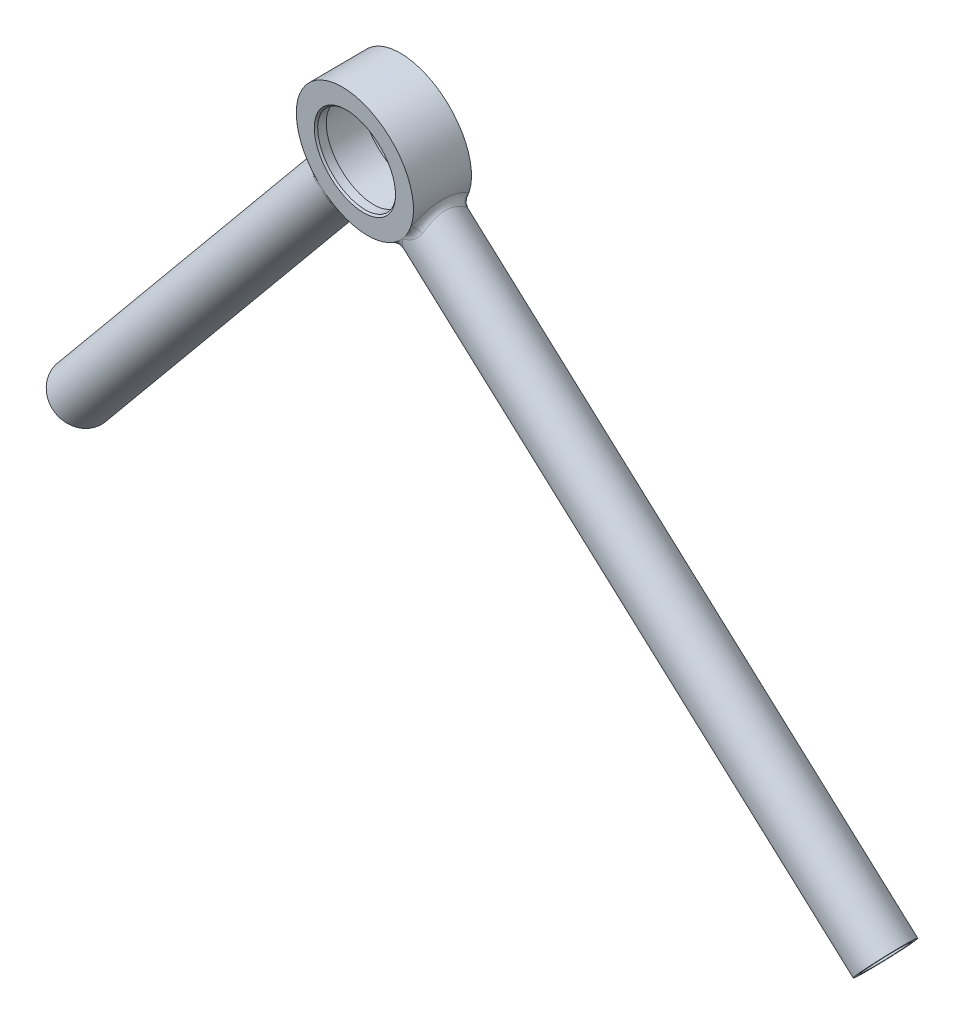
SolidWorks part; units mm, degrees
ref_plane "Ground Plane" through (0, 0, 0) normal (0, 0, 1) x (1, 0, 0)
ref_plane "Side Plane" through (0, 0, 0) normal (0, 1, 0) x (1, 0, 0)
ref_plane "Rear Axle Centerline" through (0, 0, 0) normal (1, 0, 0) x (0, 0, -1)
sketch "Chassis Side View" plane through (0, 0, 0) normal (0, 1, 0) x (1, 0, 0)
  line L0 (0, -381) -> (2300, -381) construction
  line L1 (1150, -381) -> (1150, -856.742)
  line L2 (2150, -381) -> (2150, -1062.9307) construction
  line L3 (-753.0356, 0) -> (753.0356, 0) construction
  line L4 (2450, -381) -> (2450, -1062.9307) construction
  dimension "D1" = 2300
  dimension "D2" = 475.742
  dimension "D3" = 1150
  dimension "D4" = 381
  dimension "D5" = 150
  dimension "D6" = 150
ref_plane "Front Axle Centerline" through (2300, 0, 0) normal (1, 0, 0) x (0, 0, -1)
sketch "Front Wheel Assy Constraints" plane through (2300, 0, 0) normal (1, 0, 0) x (0, 0, -1)
  line L0 (0, 727.5) -> (0, 822.5)
  line L1 (0, 822.5) -> (-271.78, 822.5)
  line L2 (-271.78, 822.5) -> (-551.18, 822.5)
  line L3 (-551.18, 822.5) -> (-551.18, 727.5)
  line L4 (-551.18, 775) -> (0, 775) construction
  line L5 (-271.78, 822.5) -> (-271.78, 775) construction
  line L6 (-551.18, 727.5) -> (-445.4516, 727.5)
  line L7 (-445.4516, 727.5) -> (-445.4516, 798.5)
  line L8 (-445.4516, 798.5) -> (-105.7284, 798.5)
  line L9 (-105.7284, 798.5) -> (-105.7284, 727.5)
  line L10 (-105.7284, 727.5) -> (0, 727.5)
  line L11 (0, 0) -> (-673.9047, 0) construction
  line L13 (0, 753.0356) -> (0, -753.0356) construction
  dimension "D1" = 95
  dimension "D2" = 279.4
  dimension "D3" = 271.78
  dimension "D4" = 23.5
  dimension "D5" = 1550
sketch "Front Sus Front View" plane through (2300, 0, 0) normal (1, 0, 0) x (0, 0, -1)
  line L0 (0, 775) -> (0, 768.65) construction
  line L1 (0, 753.0356) -> (0, -753.0356) construction
  line L2 (0, 768.65) -> (-762, 634.2888) construction
  line L3 (0, 768.65) -> (-745.3671, 768.65) construction
  line L4 (-366.7919, -1090.2477) -> (-525.9451, 520.8571) construction
  line L5 (-366.7919, -1090.2477) -> (-379.5678, 520.8571) construction
  line L6 (-366.7919, -1090.2477) -> (0, 775) construction
  line L7 (-525.9451, 520.8571) -> (-541, 673.2571)
  line L8 (-379.5678, 520.8571) -> (-381, 701.4694)
  line L9 (0, 0) -> (-152.4, 0) construction
  line L13 (-525.9451, 520.8571) -> (-379.5678, 520.8571) construction
  dimension "D1" = 6.35
  dimension "D2" = 10
  dimension "D3" = 152.4
  dimension "D4" = 1865.2477
  dimension "D7" = 541
  dimension "D8" = 153.1418
ref_plane "Fron Wheel Side View Plane" through (0, 775, 0) normal (0, 1, 0) x (1, 0, 0)
sketch "Front SVSA" plane through (0, 775, 0) normal (0, 1, 0) x (1, 0, 0)
  line L0 (2271.684, -676.7175) -> (2328.316, 133.1575)
  line L1 (2300, 0) -> (2300, -771.0839) construction
  line L2 (2300, 0) -> (-2450.054, -116.0888) construction
  line L3 (-2450.054, -116.0888) -> (2298.2335, -297.0415) construction
  line L4 (-753.0356, 0) -> (753.0356, 0) construction
  point P5 (2300, -271.78)
  dimension "D1" = 4
  dimension "D2" = 1.4
  dimension "D3" = 4750.054
sketch3d "Front Chassis Side Axes"
  line L0 (2300, 520.8571, 379.5678) -> (2300, 701.4694, 381) construction
  line L1 (2300, 520.8571, 525.9451) -> (2300, 673.2571, 541) construction
  line L2 (2300, 520.8571, 379.5678) -> (2300, 701.4694, 381) construction
  line L3 (2300, 520.8571, 525.9451) -> (2300, 673.2571, 541) construction
  line L4 (2300, 673.2571, 541) -> (2300, 775, 551.0507) construction
  line L5 (2300, 701.4694, 381) -> (2300, 775, 381.5831) construction
  line L6 (2300, 775, 0) -> (2300, 775, 771.0839) construction
  line L7 (-2450.054, 775, 116.0888) -> (2349.7917, 775, 555.6101) construction
  line L8 (-2450.054, 775, 116.0888) -> (2349.9221, 775, 384.3734) construction
  line L9 (2349.9221, 775, 384.3734) -> (2177.377, 520.8571, 372.714) construction
  line L10 (2349.7917, 775, 555.6101) -> (2225.4174, 520.8571, 519.1156) construction
  line L11 (2300, 520.8571, 525.9451) -> (2300, 520.8571, 519.1156) construction
  line L12 (2300, 520.8571, 519.1156) -> (2225.4174, 520.8571, 519.1156) construction
  line L13 (2598.7501, 520.8571, 553.3017) -> (1702.4998, 520.8571, 471.2321)
  line L14 (2300, 520.8571, 379.5678) -> (2300, 520.8571, 372.714) construction
  line L15 (2300, 520.8571, 372.714) -> (2177.377, 520.8571, 372.714) construction
  line L16 (2599.5325, 520.8571, 396.3095) -> (1700.935, 520.8571, 346.0843)
  dimension "D1" = 50
  dimension "D2" = 50
  dimension "D3" = 600
  dimension "D4" = 300
  dimension "D5" = 600
  dimension "D6" = 300
sketch3d "Front Left Control Arm"
  line L0 (2300, 520.8571, 379.5678) -> (2300, 701.4694, 381) construction
  line L2 (2300, 520.8571, 379.5678) -> (2300, 701.4694, 381) construction
  line L3 (2300, 520.8571, 525.9451) -> (2300, 673.2571, 541) construction
  line L4 (2598.7501, 520.8571, 553.3017) -> (1702.4998, 520.8571, 471.2321) construction
  line L5 (2599.5325, 520.8571, 396.3095) -> (1700.935, 520.8571, 346.0843) construction
  line L6 (2598.7501, 520.8571, 553.3017) -> (1702.4998, 520.8571, 471.2321) construction
  line L7 (2599.5325, 520.8571, 396.3095) -> (1700.935, 520.8571, 346.0843) construction
  line L8 (2450, 520.8571, 539.6806) -> (2280.5957, 673.2571, 539.2232)
  line L9 (2280.5957, 673.2571, 539.2232) -> (2150, 520.8571, 512.2097)
  line L10 (2300, 520.8571, 525.9451) -> (2300, 673.2571, 541) construction
  line L11 (2300, 673.2571, 541) -> (2280.5957, 673.2571, 539.2232) construction
  line L12 (2271.684, 775, 676.7175) -> (2328.316, 775, -133.1575) construction
  line L13 (2150, 0, 512.2097) -> (2150, 520.8571, 512.2097) construction
  line L14 (2292.3517, 701.4694, 380.5725) -> (2292.3517, 775, 381.1556) construction
  line L15 (2150, 0, 381) -> (2150, 0, 1062.9307) construction
  line L16 (2450, 0, 539.6806) -> (2450, 520.8571, 539.6806) construction
  line L17 (2450, 0, 381) -> (2450, 0, 1062.9307) construction
  line L18 (2450, 520.8571, 387.9517) -> (2292.3517, 701.4694, 380.5725)
  line L19 (2292.3517, 701.4694, 380.5725) -> (2150, 520.8571, 371.1838)
  line L20 (2300, 701.4694, 381) -> (2292.3517, 701.4694, 380.5725) construction
  line L21 (2450, 0, 387.9517) -> (2450, 520.8571, 387.9517) construction
  line L22 (2150, 0, 371.1838) -> (2150, 520.8571, 371.1838) construction
  line L23 (2280.5957, 673.2571, 539.2232) -> (2280.5957, 775, 549.2738) construction
sketch3d "Front Control Arm"
  line L0 (2450, 520.8571, 387.9517) -> (2292.3517, 701.4694, 380.5725) construction
  line L1 (2292.3517, 701.4694, 380.5725) -> (2150, 520.8571, 371.1838) construction
  line L2 (2280.5957, 673.2571, 539.2232) -> (2150, 520.8571, 512.2097) construction
  line L3 (2450, 520.8571, 539.6806) -> (2280.5957, 673.2571, 539.2232) construction
  line L4 (2450, 520.8571, 387.9517) -> (2292.3517, 701.4694, 380.5725)
  line L5 (2292.3517, 701.4694, 380.5725) -> (2150, 520.8571, 371.1838)
  line L6 (2280.5957, 673.2571, 539.2232) -> (2150, 520.8571, 512.2097)
  line L7 (2450, 520.8571, 539.6806) -> (2280.5957, 673.2571, 539.2232)
  line L8 (2450, -520.8571, 539.6806) -> (2280.5957, -673.2571, 539.2232)
  line L9 (2280.5957, -673.2571, 539.2232) -> (2150, -520.8571, 512.2097)
  line L10 (2292.3517, -701.4694, 380.5725) -> (2150, -520.8571, 371.1838)
  line L11 (2450, -520.8571, 387.9517) -> (2292.3517, -701.4694, 380.5725)
ref_plane "Max Droop Plane" through (0, 0, -25.4) normal (0, 0, 1) x (1, 0, 0)
sketch3d "Shock"
  line L0 (2292.3517, 701.4694, 380.5725) -> (2293.5626, 664.4705, 414.2387) construction
  line L1 (2300, 520.8571, 525.9451) -> (2298.2629, 520.8571, 544.9158) construction
  line L2 (2150, 520.8571, 512.2097) -> (2450, 520.8571, 539.6806) construction
  line L3 (2300, 520.8571, 525.9451) -> (2300, 230.5152, 525.9451) construction
  line L4 (2293.5626, 664.4705, 414.2387) -> (2298.2629, 520.8571, 544.9158)
  dimension "D1" = 50.038
  dimension "D2" = 19.05
sketch3d "Parametric Analysis"
  line L2 (2300, 822.5, 0) -> (2300, 822.5, 271.78) construction
  line L3 (2300.4137, 822.5, 271.7939) -> (2300.4137, 822.5, -88.8537) construction
  line L4 (2450, 520.8571, 387.9517) -> (2292.3526, 701.4695, 380.5568)
  line L5 (2292.3526, 701.4695, 380.5568) -> (2150, 520.8571, 371.1838)
  line L6 (2450, 520.8571, 539.6806) -> (2280.5972, 673.2586, 539.2077)
  line L7 (2280.5972, 673.2586, 539.2077) -> (2150, 520.8571, 512.2097)
  line L8 (2292.3517, 701.4694, 380.5725) -> (2300, 822.5, 271.78) construction
  line L9 (2450, 520.8571, 387.9517) -> (2292.3517, 701.4694, 380.5725) construction
  line L10 (2292.3517, 701.4694, 380.5725) -> (2150, 520.8571, 371.1838) construction
  line L11 (2450, 520.8571, 539.6806) -> (2280.5957, 673.2571, 539.2232) construction
  line L12 (2280.5957, 673.2571, 539.2232) -> (2150, 520.8571, 512.2097) construction
  line L13 (2280.5957, 673.2571, 539.2232) -> (2292.3517, 701.4694, 380.5725) construction
  line L14 (2300, 822.5, 271.78) -> (2280.5957, 673.2571, 539.2232) construction
  line L15 (2300, 822.5, 271.78) -> (2300.4132, 720.8156, 271.78) construction
  line L16 (2280.5972, 673.2586, 539.2077) -> (2300.4137, 822.5, 271.7939) construction
  line L17 (2300.4137, 822.5, 271.7939) -> (2292.3526, 701.4695, 380.5568) construction
  line L18 (2280.5972, 673.2586, 539.2077) -> (2292.3526, 701.4695, 380.5568) construction
  line L19 (2300.4137, 822.5, 271.7939) -> (2300.4137, 720.8148, 271.7641) construction
  line L23 (2292.3517, 701.4694, 380.5725) -> (2265.8007, 667.7821, 378.8214) construction
  line L30 (2265.8007, 667.7821, 378.8214) -> (2325.2406, 663.7898, 382.112) construction
  line L31 (2325.2406, 663.7898, 382.112) -> (2293.5626, 664.4705, 414.2387) construction
  line L32 (2292.3517, 701.4694, 380.5725) -> (2325.2406, 663.7898, 382.112) construction
  line L33 (2293.5626, 664.4705, 414.2387) -> (2265.8007, 667.7821, 378.8214) construction
  line L34 (2292.3526, 701.4695, 380.5568) -> (2293.5633, 664.4722, 414.2247) construction
  line L35 (2292.3517, 701.4694, 380.5725) -> (2293.5626, 664.4705, 414.2387) construction
  line L39 (2300.4137, 822.5, 271.7939) -> (2300.4137, 822.5798, 0.014)
  line L40 (2300.4137, 822.5798, 0.014) -> (2300.4137, 727.5798, -0.014)
  line L41 (2300, 727.5, 0) -> (2300, 822.5, 0) construction
  line L42 (2298.2629, 520.8571, 544.9158) -> (2293.5633, 664.4722, 414.2247)
  point P5 (2300.4137, 775.0798, 0)
  dimension "D1" = 25.4
  dimension "D2" = 194.2357
  dimension "D3" = 0.0798
  dimension "D4" = 0.017
sketch3d "3DSketch1"
  line L1 (2280.5972, 673.2586, 539.2077) -> (2150, 520.8571, 512.2097) construction
  line L2 (2450, 520.8571, 539.6806) -> (2280.5972, 673.2586, 539.2077) construction
  line L6 (2280.5972, 673.2586, 539.2077) -> (2150, 520.8571, 512.2097)
  line L7 (2450, 520.8571, 539.6806) -> (2280.5972, 673.2586, 539.2077)
  line L10 (2450, 520.8571, 539.6806) -> (2450, 470.0571, 539.6806) construction
  line L11 (2150, 520.8571, 512.2097) -> (2150, 470.0571, 512.2097) construction
  line L12 (2298.2629, 520.8571, 544.9158) -> (2298.2629, 470.0571, 544.9158) construction
  line L27 (2300, 775, 551.18) -> (2300, 775, 0) construction
  dimension "D1" = 50.8
  dimension "D2" = 304.9478
  dimension "D3" = 544.9185
ref_plane "Plane1" through (0, 718.612, 0) normal (0, 1, 0) x (1, 0, 0)
ref_plane "Plane3" through (-23.7383, -25.582, 259.237) normal (-0.0908, -0.0978, 0.9911) x (0.9959, -0.0089, 0.0903)
sketch "Sketch3" plane through (-23.7383, -25.582, 259.237) normal (-0.0908, -0.0978, 0.9911) x (0.9959, -0.0089, 0.0903)
  circle A0 centre (2313.8835, 722.9571) radius 19.05
  dimension "D1" = 38.1
extrude "Boss-Extrude1" add sketch "Sketch3" along normal mid plane 15.875
sketch "Sketch4" plane through (-24.4586, -26.3583, 267.1036) normal (-0.0908, -0.0978, 0.9911) x (0.9959, -0.0089, 0.0903)
  circle A0 centre (2313.8835, 722.9571) radius 12.7
  dimension "D1" = 25.4
extrude "Cut-Extrude1" cut sketch "Sketch4" against normal blind 15.875
sketch "Sketch5" plane through (-23.7383, -25.582, 259.237) normal (-0.0908, -0.0978, 0.9911) x (0.9959, -0.0089, 0.0903)
  line L0 (2313.8835, 722.9571) -> (2182.7452, 568.6409) construction
  line L1 (2483.9882, 571.3387) -> (2313.8835, 722.9571) construction
  point P0 (2280.9874, 684.2468)
  point P1 (2351.806, 689.1559)
  dimension "D1" = 50.8
  dimension "D2" = 50.8
sketch "Sketch12" plane through (-23.7383, -25.582, 259.237) normal (-0.0908, -0.0978, 0.9911) x (0.9959, -0.0089, 0.0903)
  line L0 (2313.8835, 722.9571) -> (2182.7452, 568.6409) construction
  line L1 (2483.9882, 571.3387) -> (2313.8835, 722.9571) construction
  point P0 (2200.5604, 589.6049)
  point P1 (2463.4509, 589.6441)
  dimension "D1" = 174.9998
  dimension "D2" = 200.3566
ref_plane "Plane4" through (2167.7417, 541.561, 515.8774) normal (-0.6449, -0.7526, -0.1333) x (-0.7643, 0.635, 0.1125)
ref_plane "Plane5" through (2429.5474, 539.2571, 539.6235) normal (-0.7434, 0.6688, -0.0021) x (-0.0015, 0.0014, 1)
sketch "Sketch6" plane through (2167.7417, 541.561, 515.8774) normal (-0.6449, -0.7526, -0.1333) x (-0.7643, 0.635, 0.1125)
  circle A0 centre (0, 0) radius 7.9375
  circle A1 centre (0, 0) radius 6.35
  dimension "D1" = 15.875
extrude "Boss-Extrude2" add sketch "Sketch6" against normal up to body
sketch "Sketch7" plane through (2429.5474, 539.2571, 539.6235) normal (-0.7434, 0.6688, -0.0021) x (-0.0015, 0.0014, 1)
  circle A0 centre (0, 0) radius 7.9375
  circle A1 centre (0, 0) radius 6.35
  dimension "D1" = 15.875
extrude "Boss-Extrude3" add sketch "Sketch7" along normal up to body
fillet "Fillet1" radius 2.54 4 edges at (2288.2371, 655.8515, 537.9491) (2263.3363, 665.0976, 538.3666) (2263.3363, 665.0976, 538.3666) (2288.2371, 655.8515, 537.9491)
ref_plane "Plane6" through (1321.5606, 1542.207, 273.2032) normal (-0.6449, -0.7526, -0.1333) x (-0.7643, 0.635, 0.1125)
sketch "Sketch10" plane through (1321.5606, 1542.207, 273.2032) normal (-0.6449, -0.7526, -0.1333) x (-0.7643, 0.635, 0.1125)
  line L0 (-1255.7722, -405.6199) -> (-1253.8872, -421.3826) construction
  line L1 (-1243.1621, -404.1119) -> (-1268.3824, -407.1279) construction
  line L2 (-1266.4974, -422.8906) -> (-1241.2771, -419.8745) construction
  line L4 (-1235.9145, -411.2392) -> (-1254.8297, -413.5012) construction
  line L5 (-1234.972, -419.1205) -> (-1236.857, -403.3578) construction
  line L6 (-1246.1002, -404.4632) -> (-1241.5858, -403.9233)
  line L14 (-1241.5858, -403.9233) -> (-1241.4652, -404.9322)
  line L15 (-1241.4652, -404.9322) -> (-1240.9355, -404.8688)
  line L16 (-1240.9355, -404.8688) -> (-1240.8089, -405.9281)
  line L17 (-1240.8089, -405.9281) -> (-1241.3385, -405.9914)
  line L18 (-1244.553, -417.4012) -> (-1246.1002, -404.4632)
  line L19 (-1240.0386, -416.8614) -> (-1244.553, -417.4012)
  line L20 (-1241.3385, -405.9914) -> (-1240.0386, -416.8614)
  line L21 (-1271.9648, -423.5444) -> (-1234.972, -419.1205) construction
  dimension "D1" = 14.2875
  dimension "D2" = 14.8209
  dimension "D3" = 14.2875
  dimension "D4" = 2.8448
  dimension "D5" = 4.5466
  dimension "D6" = 1.016
  dimension "D7" = 1.0668
revolve "Cut-Revolve1" cut sketch "Sketch10" angle 360 about L0
chamfer "Chamfer3" distance 0.508 angle 45 2 edges at (2281.3175, 688.2534, 532.7443) (2279.8768, 659.8437, 545.827)
equation "\"wheelbase\"= 2.3m"
equation "\"track_front_outer\"= 1.55m"
equation "\"cg_h\"= 18.73in"
equation "\"cg_b\"= \"wheelbase\" / 2"
equation "\"chassis_ride_height\"= 15in"
equation "\"hub_offset\"= 23.5mm"
equation "\"tire_radius\"= 11in"
equation "\"tire_radius_loaded\"= 10.7in"
equation "\"tire_width\"= 95mm"
equation "\"static_camber\"= 0deg"
equation "\"caster_static\"= 4deg"
equation "\"control_arm_ratio\"= 0.95"
equation "\"roll_center_height\"= 6in"
equation "\"scrub_radius\"= 0.25in"
equation "\"camber_change_rate\"= 0.5deg'per inch of travel"
equation "\"fvsa_length\"= atn ( 1 / \"camber_change_rate\" )"
equation "\"svsa_length\"= 2.5 * \"wheelbase\""
equation "\"svsa_height\"= 1"
equation "\"anti_squat_rear\"= 0.15"
equation "\"front_brakes\"= .75"
equation "\"anti_dive_front\"= 0.1"
equation "\"D1@Chassis Side View\" = \"wheelbase\""
equation "\"D2@Chassis Side View\" = \"cg_h\""
equation "\"D3@Chassis Side View\" = \"cg_b\""
equation "\"D4@Chassis Side View\" = \"chassis_ride_height\""
equation "\"D1@Front Axle Centerline\"=\"wheelbase\""
equation "\"D1@Front Wheel Assy Constraints\" = \"tire_width\""
equation "\"D2@Front Wheel Assy Constraints\" = \"tire_radius\""
equation "\"D3@Front Wheel Assy Constraints\" = \"tire_radius_loaded\""
equation "\"D4@Front Wheel Assy Constraints\" = \"hub_offset\""
equation "\"D1@Front Sus Front View\" = \"scrub_radius\""
equation "\"static_kingpin\"= 10deg"
equation "\"D2@Front Sus Front View\" = \"static_kingpin\""
equation "\"D3@Front Sus Front View\" = \"roll_center_height\""
equation "\"D6@Front Sus Front View\" = \"chassis_ride_height\""
equation "\"D7@Front Sus Front View\"=\"chassis_ride_height\" + 160mm"
equation "\"D1@Front SVSA\" = \"caster_static\""
equation "\"D4@Front Sus Front View\"=\"fvsa_length\"+10"
equation "\"D5@Front Wheel Assy Constraints\"=\"track_front_outer\""
equation "\"phi_front\"= atn ( \"anti_dive_front\" / \"front_brakes\" * \"cg_h\" / \"wheelbase\" )"
equation "\"anti_lift_rear\"= 0.1"
equation "\"a\"= 0"
